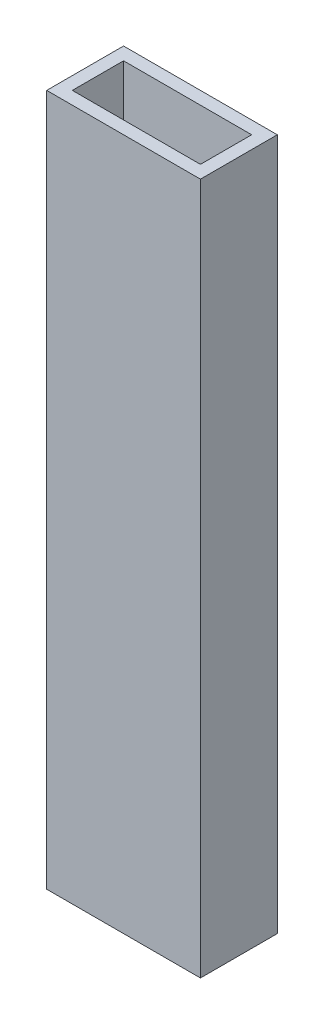
SolidWorks part; units mm, degrees
ref_plane "Front Plane" through (0, 0, 0) normal (0, 0, 1) x (1, 0, 0)
ref_plane "Top Plane" through (0, 0, 0) normal (0, 1, 0) x (1, 0, 0)
ref_plane "Right Plane" through (0, 0, 0) normal (1, 0, 0) x (0, 0, -1)
sketch "Sketch1" plane through (0, 0, 0) normal (0, 1, 0) x (1, 0, 0)
  line L0 (3.175, 15.875) -> (34.925, 15.875)
  line L1 (0, 0) -> (38.1, 0)
  line L2 (0, 0) -> (0, 19.05)
  line L3 (0, 19.05) -> (38.1, 19.05)
  line L4 (38.1, 0) -> (38.1, 19.05)
  line L5 (34.925, 3.175) -> (34.925, 15.875)
  line L6 (3.175, 3.175) -> (34.925, 3.175)
  line L7 (3.175, 3.175) -> (3.175, 15.875)
  dimension "D1" = 38.1
  dimension "D2" = 19.05
extrude "Boss-Extrude1" add sketch "Sketch1" along normal blind 171.45
